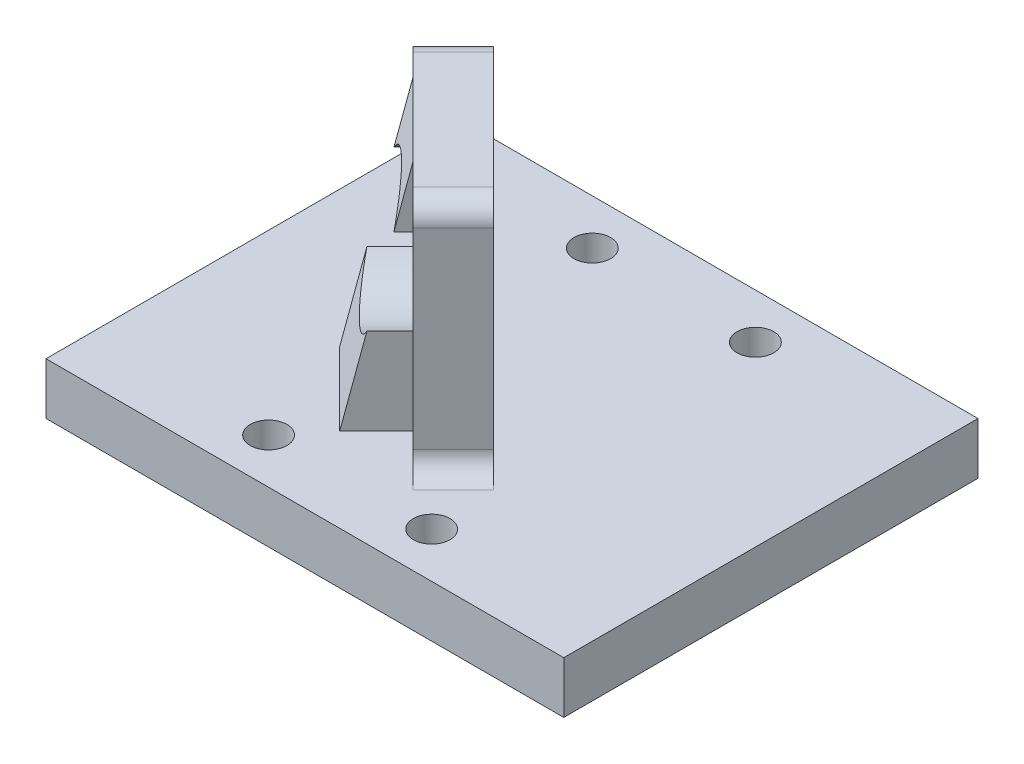
SolidWorks part; units mm, degrees
material "PLA Black"
ref_plane "Front Plane" through (0, 0, 0) normal (0, 0, 1) x (1, 0, 0)
ref_plane "Top Plane" through (0, 0, 0) normal (0, 1, 0) x (1, 0, 0)
ref_plane "Right Plane" through (0, 0, 0) normal (1, 0, 0) x (0, 0, -1)
sketch "Sketch1" plane through (0, 0, 0) normal (0, 1, 0) x (1, 0, 0)
  line L1 (-31.75, -25.4) -> (31.75, -25.4)
  line L2 (-31.75, -25.4) -> (-31.75, 25.4)
  line L3 (-31.75, 25.4) -> (31.75, 25.4)
  line L4 (31.75, -25.4) -> (31.75, 25.4)
  line L5 (-31.75, -25.4) -> (31.75, 25.4) construction
  line L6 (-31.75, 25.4) -> (31.75, -25.4) construction
  point P0 (0, 0)
  dimension "D1" = 63.5
  dimension "D2" = 50.8
extrude "Boss-Extrude1" add sketch "Sketch1" along normal blind 6.35
sketch "Sketch2" plane through (0, 6.35, 0) normal (0, 1, 0) x (1, 0, 0)
  line L0 (2.908, -15.0525) -> (-15.0525, 2.908)
  line L1 (2.908, -15.0525) -> (7.8577, -10.1028)
  line L2 (-15.0525, 2.908) -> (-10.1028, 7.8577)
  line L3 (7.8577, -10.1028) -> (-10.1028, 7.8577)
  line L4 (2.908, -15.0525) -> (-10.1028, 7.8577) construction
  line L5 (-15.0525, 2.908) -> (7.8577, -10.1028) construction
  line L6 (31.75, 25.4) -> (-31.75, 25.4) construction
  line L7 (0, 0) -> (-35355.3391, 35355.3391) construction
  line L8 (-3.5974, -3.5974) -> (0, 0) construction
  point P1 (-3.5974, -3.5974)
  dimension "D1" = 3.175
  dimension "D2" = 25.4
  dimension "D3" = 7
  dimension "D4" = 135
extrude "Boss-Extrude2" add sketch "Sketch2" along normal blind 28.575
ref_plane "Plane1" through (0, 0, 0) normal (0.7071, 0, -0.7071) x (-0.7071, 0, -0.7071)
sketch "Sketch4" plane through (0, 6.35, 0) normal (0, 1, 0) x (1, 0, 0)
  line L4 (-10, -19.85) -> (10, 19.85) construction
  circle A0 centre (10, -19.85) radius 2.25
  circle A1 centre (10, 19.85) radius 2.25
  circle A2 centre (-10, 19.85) radius 2.25
  circle A3 centre (-10, -19.85) radius 2.25
  point P8 (0, 0)
  dimension "D2" = 4.5
  dimension "D1" = 39.7
  dimension "D5" = 20
extrude "Cut-Extrude2" cut sketch "Sketch4" against normal through all
fillet "Fillet1" radius 2.54 4 edges at (-12.5777, 6.35, -5.3828) (-12.5777, 34.925, -5.3828) (5.3828, 34.925, 12.5777) (5.3828, 6.35, 12.5777)
sketch "Sketch5" plane through (-1.1225, 0, 1.1225) normal (0.7071, 0, -0.7071) x (-0.7071, 0, -0.7071)
  line L0 (-10.16, 34.925) -> (10.16, 34.925) construction
  circle A0 centre (0, 22.225) radius 5.08
  point P6 (0, 34.925)
  dimension "D1" = 10.16
  dimension "D2" = 12.7
ref_plane "Plane2" through (0, 0, 0) normal (-0.7071, 0, -0.7071) x (-0.7071, 0, 0.7071)
extrude "Cut-Extrude3" cut sketch "Sketch5" against normal through all
sketch "Sketch6" plane through (0, 0, 0) normal (-0.7071, 0, -0.7071) x (-0.7071, 0, 0.7071)
  line L0 (8.5875, 34.925) -> (14.9375, 6.35)
  line L1 (14.9375, 6.35) -> (8.5875, 6.35)
  line L2 (8.5875, 6.35) -> (8.5875, 34.925)
  dimension "D1" = 6.35
extrude "Boss-Extrude3" add sketch "Sketch6" along normal mid plane 12.7
sketch "Sketch7" plane through (-6.0723, 0, 6.0723) normal (-0.7071, 0, 0.7071) x (0.7071, 0, 0.7071)
  circle A0 centre (0, 22.225) radius 5.08 construction
  circle A1 centre (0, 22.225) radius 5.08 construction
  circle A2 centre (0, 22.225) radius 8.255
  dimension "D1" = 3.175
extrude "Cut-Extrude4" cut sketch "Sketch7" along normal through all
